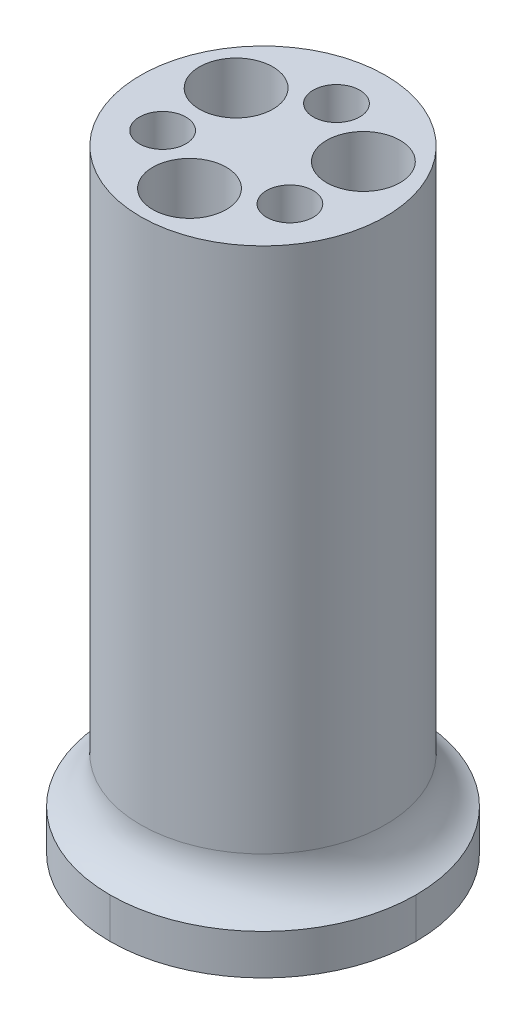
SolidWorks part; units mm, degrees
ref_plane "前视基准面" through (0, 0, 0) normal (0, 0, 1) x (1, 0, 0)
ref_plane "上视基准面" through (0, 0, 0) normal (0, 1, 0) x (1, 0, 0)
ref_plane "右视基准面" through (0, 0, 0) normal (1, 0, 0) x (0, 0, -1)
other "Configuration Table"
sketch "草图1" plane through (0, 0, 0) normal (0, 1, 0) x (1, 0, 0)
  circle A0 centre (0, 0) radius 10
  dimension "D1" = 20
extrude "凸台-拉伸1" add sketch "草图1" along normal blind 30
sketch "草图2" plane through (0, 30, 0) normal (0, 1, 0) x (1, 0, 0)
  circle A0 centre (0, 0) radius 6
  circle A1 centre (0, 6) radius 1.85
  circle A2 centre (5.1962, 3) radius 1.85
  circle A3 centre (5.1962, -3) radius 1.85
  circle A4 centre (0, -6) radius 1.85
  circle A5 centre (-5.1962, -3) radius 1.85
  circle A6 centre (-5.1962, 3) radius 1.85
  point P17 (0, 0)
  dimension "D1" = 12
  dimension "D2" = 3.7
  dimension "D3" = 6
extrude "切除-拉伸1" cut sketch "草图2" against normal through all contours A6 | A1 | A2 | A3 | A4 | A5
sketch "草图3" plane through (0, 30, 0) normal (0, 1, 0) x (1, 0, 0)
  circle A0 centre (0, 6) radius 1.85
  circle A1 centre (-5.1962, -3) radius 1.85
  circle A2 centre (5.1962, -3) radius 1.85
  circle A3 centre (0, 6) radius 1.6
  circle A4 centre (-5.1962, -3) radius 1.6
  circle A5 centre (5.1962, -3) radius 1.6
  dimension "D1" = 3.2
  dimension "D2" = 3.2
  dimension "D3" = 3.2
extrude "凸台-拉伸2" add sketch "草图3" against normal blind 15
sketch "草图4" plane through (0, 0, 0) normal (0, -1, 0) x (1, 0, 0)
  circle A0 centre (-5.1962, 3) radius 1.85
  circle A1 centre (-5.1962, 3) radius 2.5
  circle A2 centre (5.1962, 3) radius 1.85
  circle A3 centre (5.1962, 3) radius 2.5
  circle A4 centre (0, -6) radius 1.85
  circle A5 centre (0, -6) radius 2.5
  dimension "D1" = 5
  dimension "D2" = 5
  dimension "D3" = 5
extrude "切除-拉伸2" cut sketch "草图4" against normal blind 15
sketch "草图5" plane through (0, 0, 0) normal (0, -1, 0) x (1, 0, 0)
  circle A0 centre (0, 6) radius 1.85
  circle A1 centre (-5.1962, -3) radius 1.85
  circle A2 centre (5.1962, -3) radius 1.85
  circle A3 centre (-5.1962, -3) radius 1.6
  circle A4 centre (5.1962, -3) radius 1.6
  circle A5 centre (0, 6) radius 1.6
  dimension "D1" = 3.2
  dimension "D2" = 3.2
  dimension "D3" = 3.2
extrude "凸台-拉伸3" add sketch "草图5" against normal blind 15
sketch "草图6" plane through (0, 30, 0) normal (0, 1, 0) x (1, 0, 0)
  circle A0 centre (-5.1962, 3) radius 2.5
  circle A1 centre (5.1962, 3) radius 2.5
  circle A2 centre (0, -6) radius 2.5
  dimension "D1" = 5
  dimension "D2" = 5
  dimension "D3" = 5
extrude "切除-拉伸4" cut sketch "草图6" against normal blind 15
sketch "草图8" plane through (0, 0, 0) normal (0, -1, 0) x (1, 0, 0)
  line L1 (-12.5, -12.5) -> (12.5, -12.5)
  line L2 (-12.5, -12.5) -> (-12.5, 12.5)
  line L3 (-12.5, 12.5) -> (12.5, 12.5)
  line L4 (12.5, -12.5) -> (12.5, 12.5)
  line L5 (-12.5, -12.5) -> (12.5, 12.5) construction
  line L6 (-12.5, 12.5) -> (12.5, -12.5) construction
  circle A0 centre (0, 0) radius 10
  point P0 (0, 0)
  dimension "D1" = 25
  dimension "D2" = 25
extrude "凸台-拉伸4" add sketch "草图8" against normal blind 3
fillet "圆角1" radius 4 1 edges at (0, 3, -10) type face fillet first side face at (0, 3, -10) second side face at (0, 3, -10)
fillet "圆角6" radius 12.5 1 edges at (12.5, 1.5, 12.5) type face fillet first side face at (12.5, 2.0413, 0.2825) second side face at (-0.2825, 2.0413, 12.5)
fillet "圆角7" radius 12.5 1 edges at (-12.5, 1.5, 12.5) type face fillet first side face at (-5.6305, 1.8876, 12.5) second side face at (-12.5, 2.0413, -0.2825)
fillet "圆角8" radius 12.5 1 edges at (-12.5, 1.5, -12.5) type face fillet first side face at (-12.5, 1.8876, -5.6305) second side face at (0.2825, 2.0413, -12.5)
fillet "圆角9" radius 12.5 1 edges at (12.5, 1.5, -12.5) type face fillet first side face at (5.6305, 1.8876, -12.5) second side face at (12.5, 1.8292, -6.8914)
sketch "草图9" plane through (0, 0, 0) normal (0, -1, 0) x (1, 0, 0)
  circle A0 centre (5.1962, 3) radius 2.5
  circle A1 centre (-5.1962, 3) radius 2.5
  circle A2 centre (0, -6) radius 2.5
extrude "凸台-拉伸6" add sketch "草图9" against normal blind 25
sketch "草图10" plane through (0, 30, 0) normal (0, 1, 0) x (1, 0, 0)
  circle A0 centre (0, 6) radius 1.9
  circle A1 centre (-5.1962, -3) radius 1.9
  circle A2 centre (5.1962, -3) radius 1.9
  dimension "D1" = 3.8
  dimension "D2" = 3.8
  dimension "D3" = 3.8
extrude "切除-拉伸5" cut sketch "草图10" against normal blind 10
sketch "草图11" plane through (0, 30, 0) normal (0, 1, 0) x (1, 0, 0)
  circle A0 centre (-5.1962, 3) radius 3
  circle A1 centre (5.1962, 3) radius 3
  circle A2 centre (0, -6) radius 3
  dimension "D1" = 6
  dimension "D2" = 6
  dimension "D3" = 6
extrude "切除-拉伸6" cut sketch "草图11" against normal blind 15
sketch "草图13" plane through (0, 30, 0) normal (0, 1, 0) x (1, 0, 0)
  circle A0 centre (0, 0) radius 10
  circle A1 centre (-5.1962, 3) radius 3
  circle A2 centre (0, 6) radius 1.9
  circle A3 centre (5.1962, 3) radius 3
  circle A4 centre (0, -6) radius 3
  circle A5 centre (5.1962, -3) radius 1.9
  circle A6 centre (-5.1962, -3) radius 1.9
extrude "凸台-拉伸7" add sketch "草图13" along normal blind 20
